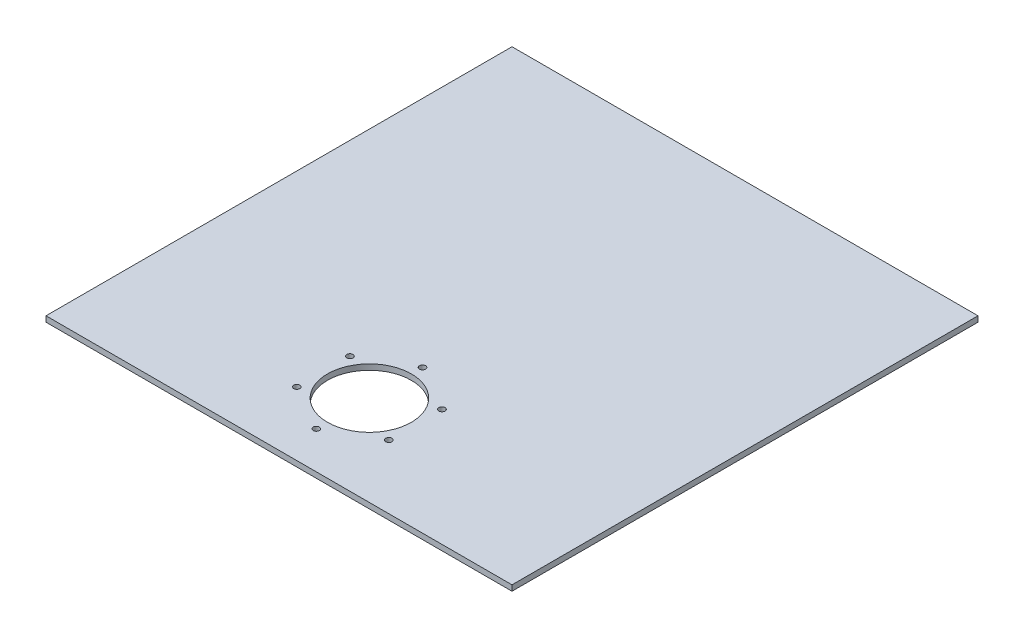
SolidWorks part; units mm, degrees
note: '?' marks a value the reader was unsure of.
ref_plane "前视基准面" through (0, 0, 0) normal (0, 0, 1) x (1, 0, 0)
ref_plane "上视基准面" through (0, 0, 0) normal (0, 1, 0) x (1, 0, 0)
ref_plane "右视基准面" through (0, 0, 0) normal (1, 0, 0) x (0, 0, -1)
sketch "草图1" plane through (0, 0, 0) normal (0, 1, 0) x (1, 0, 0)
  line L1 (-125, -125) -> (125, -125)
  line L2 (-125, -125) -> (-125, 125)
  line L3 (-125, 125) -> (125, 125)
  line L4 (125, -125) -> (125, 125)
  line L5 (-125, -125) -> (125, 125) construction
  line L6 (-125, 125) -> (125, -125) construction
  point P0 (0, 0)
  dimension "D1" = 250
  dimension "D2" = 250
extrude "凸台-拉伸1" add sketch "草图1" along normal blind 3
sketch "草图2" plane through (0, 3, 0) normal (0, 1, 0) x (1, 0, 0)
  line L0 (-125, -28) -> (125, -28)
  line L1 (-125, 125) -> (-125, -125) construction
  line L2 (125, -125) -> (125, 125) construction
  line L3 (-125, -125) -> (125, -125) construction
  line L4 (-125, -28) -> (-125, -125)
  line L5 (-125, -76.5) -> (125, -76.5)
  circle A0 centre (0, -76.5) radius 28.5
  dimension "D2" = 57
  dimension "D1" = 97
sketch "草图3" plane through (0, 3, 0) normal (0, 1, 0) x (1, 0, 0)
  circle A0 centre (0, -76.5) radius 28.5 construction
  point P0 (0, -48)
hole_wizard "孔1" positions "草图3" profile "草图4" legacy end condition up to next
sketch "草图4" plane through (0, 3, 48) normal (1, 0, 0) x (0, 0, 1)
  line L0 (0, 0) -> (0, 3)
  line L1 (0, 3) -> (1.65, 3)
  line L2 (1.65, 3) -> (1.65, 0)
  line L3 (1.65, 0) -> (0, 0)
  line L4 (0, 110) -> (0, -10) construction
  dimension "直径" = 3.3
  dimension "深度" = 3
ref_axis "基准轴1" through (0, 3, 76.5) along (0, 1, 0)?
pattern_circular "阵列(圆周)1" count 6 every 60 about axis through (0, 0, 76.5) along (0, 1, 0) of "孔1"
sketch "草图5" plane through (0, 3, 0) normal (0, 1, 0) x (1, 0, 0)
  line L0 (-125, -76.5) -> (125, -76.5) construction
  circle A0 centre (0, -76.5) radius 22.5
  dimension "D1" = 45
extrude "切除-拉伸1" cut sketch "草图5" against normal blind 10
